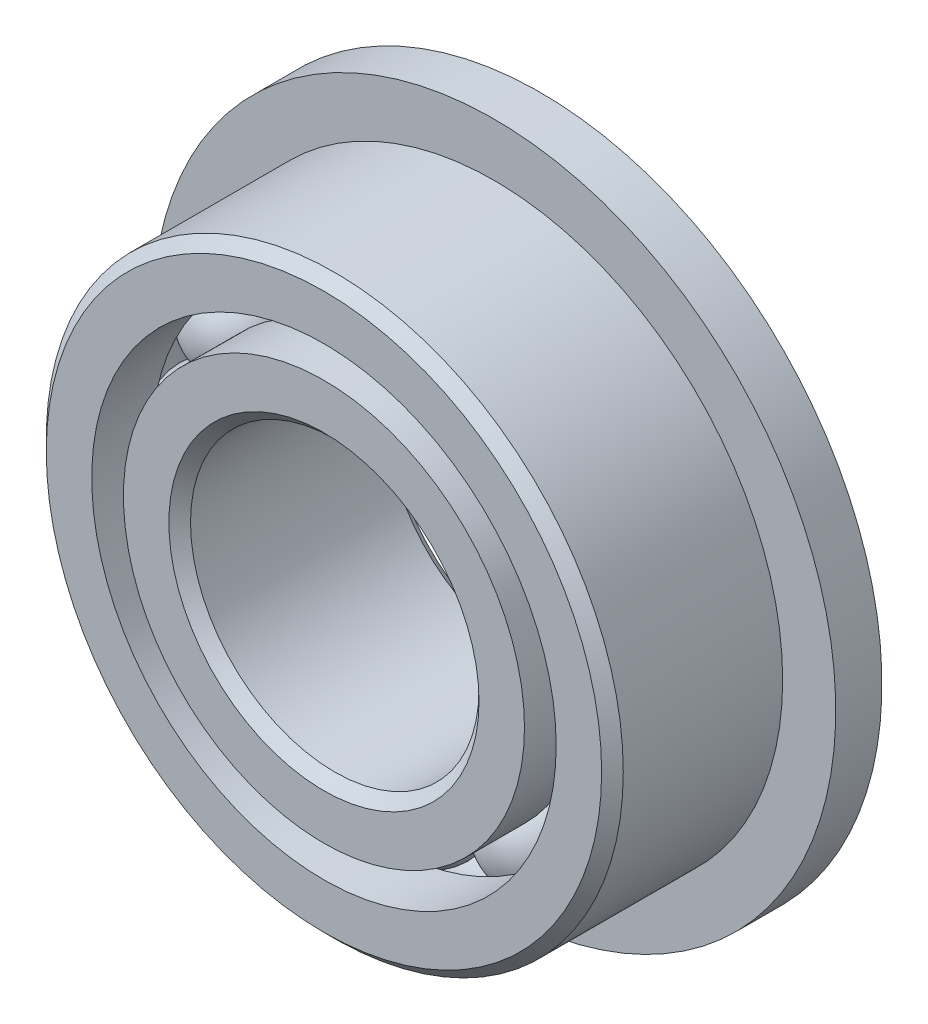
SolidWorks part; units mm, degrees
ref_plane "Front Plane" through (0, 0, 0) normal (0, 0, 1) x (1, 0, 0)
ref_plane "Top Plane" through (0, 0, 0) normal (0, 1, 0) x (1, 0, 0)
ref_plane "Right Plane" through (0, 0, 0) normal (1, 0, 0) x (0, 0, -1)
sketch "Sketch1" plane through (0, 0, 0) normal (1, 0, 0) x (0, 0, -1)
  line L0 (-1.1906, 0) -> (1.1906, 0) construction
  line L1 (0, 3.175) -> (0, -3.175) construction
  line L2 (1.0716, 3.175) -> (-1.0716, 3.175)
  line L3 (-1.0716, 3.175) -> (-1.1906, 3.0559)
  line L4 (-1.1906, 3.0559) -> (-1.1906, 2.5557)
  line L5 (-1.1906, 2.5557) -> (-0.5292, 2.5557)
  line L6 (1.1906, 2.5557) -> (0.5292, 2.5557)
  line L7 (1.1906, 3.0559) -> (1.1906, 2.5557)
  line L8 (1.0716, 3.175) -> (1.1906, 3.0559)
  line L9 (0, 3.175) -> (0, 2.3813) construction
  line L10 (0, 2.3813) -> (0, 1.5875) construction
  arc A0 (-0.5292, 2.5557) -> (0.5292, 2.5557) centre (0, 2.3813) cw
  point P14 (0, 1.5875)
  dimension "OD" = 6.35
  dimension "D1" = 45
  dimension "D2" = 0.1191
  dimension "Shaft Dia" = 3.175
  dimension "D3" = 1.0583
  dimension "D4" = 0.1745
  dimension "Width" = 2.3813
revolve "Revolve1" add sketch "Sketch1" angle 360 about L0
sketch "Sketch3" plane through (0, 0, 0) normal (1, 0, 0) x (0, 0, -1)
  line L0 (-1.0716, 3.175) -> (-1.1906, 3.0559) construction
  line L1 (-0.5292, 2.2068) -> (-1.1906, 2.2068)
  line L2 (-1.1906, 3.0559) -> (-1.1906, 2.5557) construction
  line L3 (-1.1906, 2.2068) -> (-1.1906, 1.7066)
  line L5 (-1.1906, 1.7066) -> (-1.0716, 1.5875)
  line L6 (-1.0716, 1.5875) -> (1.0716, 1.5875)
  line L7 (1.1906, 3.0559) -> (1.1906, 2.5557) construction
  line L8 (1.0716, 1.5875) -> (1.1906, 1.7066)
  line L10 (1.1906, 1.7066) -> (1.1906, 2.2068)
  line L11 (1.1906, 2.2068) -> (0.5292, 2.2068)
  line L13 (1.0716, 3.175) -> (1.1906, 3.0559) construction
  arc A1 (0.5292, 2.2068) -> (-0.5292, 2.2068) centre (0, 2.3812) cw
  arc A2 (0.5292, 2.5557) -> (-0.5292, 2.5557) centre (0, 2.3813) ccw construction
revolve "Revolve3" add sketch "Sketch3" angle 360 about L0
sketch "Sketch5" plane through (0, 0, 0) normal (1, 0, 0) x (0, 0, -1)
  line L0 (1.1906, 3.0559) -> (1.1906, 2.5557) construction
  line L1 (1.1906, 2.8058) -> (0.6826, 2.8058)
  line L2 (1.1906, 2.8058) -> (1.1906, 3.7592)
  line L3 (1.1906, 3.7592) -> (0.6826, 3.7592)
  line L4 (0.6826, 2.8058) -> (0.6826, 3.7592)
  line L5 (1.1906, 0) -> (-1.1906, 0) construction
  dimension "Th" = 0.508
  dimension "Flange OD" = 7.5184
revolve "Revolve5" add sketch "Sketch5" angle 360 about L5
sketch "Sketch4" plane through (0, 0, 0) normal (1, 0, 0) x (0, 0, -1)
  line L0 (-0.5572, 2.3812) -> (0.5572, 2.3812)
  arc A2 (-0.5572, 2.3812) -> (0.5572, 2.3812) centre (0, 2.3813) cw
  arc A3 (0.5292, 2.5557) -> (-0.5292, 2.5557) centre (0, 2.3813) ccw construction
revolve "Revolve4" add sketch "Sketch4" angle 360 about L0
ref_axis "Axis1" through (0, 0, -1.1906) along (0, 0, 1)
pattern_circular "CirPattern1" count 12 every 30 about axis through (0, 0, -1.1906) along (0, 0, 1) of bodies 104
equation "\"D2@Sketch1\" = \"Width@Sketch1\"*.05"
equation "\"D3@Sketch1\" = \"Width@Sketch1\"/2.25"
equation "\"D4@Sketch1\" = (((\"OD@Sketch1\"-\"Width@Sketch1\")/2)/3.25)/3.5"
equation "\"D2@CirPattern1\" = 360/\"Balls@CirPattern1\""
